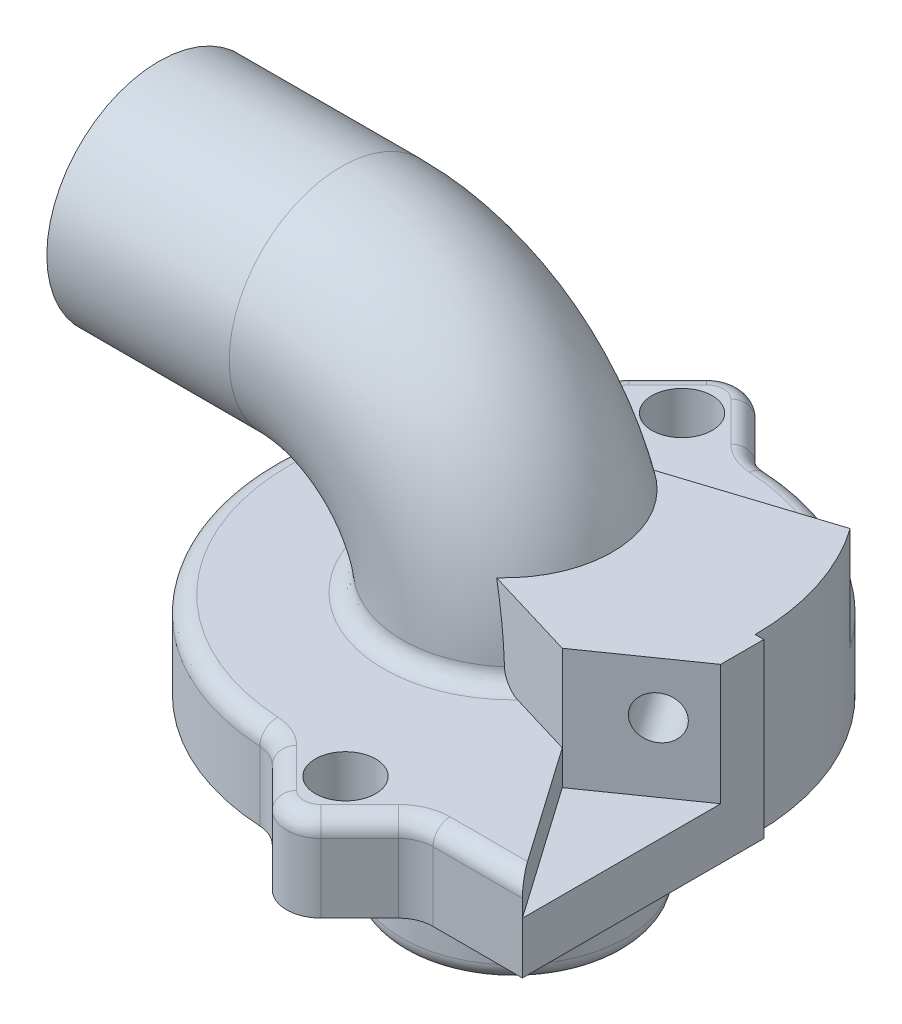
SolidWorks part; units mm, degrees
ref_plane "Front Plane" through (0, 0, 0) normal (0, 0, 1) x (1, 0, 0)
ref_plane "Top Plane" through (0, 0, 0) normal (0, 1, 0) x (1, 0, 0)
ref_plane "Right Plane" through (0, 0, 0) normal (1, 0, 0) x (0, 0, -1)
sketch "Sketch1" plane through (0, 0, 0) normal (0, 1, 0) x (1, 0, 0)
  circle A0 centre (0, 0) radius 14
  circle A1 centre (0, 0) radius 4.5
  dimension "D1" = 28
  dimension "D2" = 9
extrude "Boss-Extrude1" add sketch "Sketch1" along normal blind 5
sketch "Sketch5" plane through (0, 5, 0) normal (0, 1, 0) x (1, 0, 0)
  line L0 (0, -14) -> (4.2426, -18.2426)
  line L1 (14.5, -14) -> (14.5, 0)
  line L2 (14.5, 0) -> (14, 0)
  line L3 (14, 0) -> (0, -14)
  line L4 (4.2426, -18.2426) -> (8.4853, -14)
  line L5 (-2.75, 0) -> (2.75, 0) construction
  line L6 (0, -2.75) -> (0, 2.75) construction
  line L7 (8.4853, -14) -> (14.5, -14)
  line L8 (0, 14) -> (-4.2426, 18.2426)
  line L9 (-4.2426, 18.2426) -> (-8.4853, 14)
  line L10 (-8.4853, 14) -> (-8.4853, 11.1355)
  line L11 (-8.4853, 11.1355) -> (0, 14)
  circle A2 centre (0, 0) radius 14 construction
  dimension "D1" = 14.5
  dimension "D2" = 6
  dimension "D3" = 6
  dimension "D4" = 90
  dimension "D5" = 6
  dimension "D6" = 6
  dimension "D7" = 135
extrude "Boss-Extrude3" add sketch "Sketch5" against normal blind 5
sketch "Sketch6" plane through (0, 0, 0) normal (0, -1, 0) x (1, 0, 0)
  circle A0 centre (0, 0) radius 4.5
  circle A1 centre (0, 0) radius 6.5
  circle A2 centre (0, 0) radius 4.5 construction
  dimension "D1" = 2
extrude "Boss-Extrude4" add sketch "Sketch6" along normal blind 10
sketch "Sketch9" plane through (0, 5, 0) normal (0, 1, 0) x (1, 0, 0)
  line L0 (4.2426, -18.2426) -> (8.4853, -14) construction
  line L1 (0, -14) -> (4.2426, -18.2426) construction
  line L2 (-4.2426, 18.2426) -> (-8.4853, 14) construction
  line L3 (0, 14) -> (-4.2426, 18.2426) construction
  circle A0 centre (4.2426, -14) radius 1.75
  circle A1 centre (-4.2426, 14) radius 1.75
  dimension "D1" = 3.5
  dimension "D2" = 3
  dimension "D3" = 3
  dimension "D5" = 3
  dimension "D4" = 3
extrude "Cut-Extrude2" cut sketch "Sketch9" against normal blind 10
sketch "Sketch11" plane through (0, 5, 0) normal (0, 1, 0) x (1, 0, 0)
  line L0 (14.5, -14) -> (9.0968, -6.2834)
  line L1 (9.0968, -6.2834) -> (14.5, -2.5)
  line L3 (14.5, -14) -> (14.5, 0) construction
  line L4 (14.5, -2.5) -> (18.671, -8.4568) construction
  line L5 (14.5, -14) -> (14.5, -2.5)
  dimension "D1" = 35
  dimension "D2" = 11.5
extrude "Cut-Extrude3" cut sketch "Sketch11" against normal blind 2 contours L1 L5 L0
sketch "Sketch12" plane through (0, 5, 0) normal (0, 1, 0) x (1, 0, 0)
  line L0 (9.0968, -6.2834) -> (14.5, -2.5)
  line L1 (14.5, -2.5) -> (14.5, 0)
  line L2 (-8.25, 0) -> (8.25, 0) construction
  line L3 (14.5, 0) -> (14, 0)
  line L4 (9.0968, -6.2834) -> (3.1625, -4.4998)
  line L6 (2.0997, 5.0834) -> (11.4366, 8.075)
  arc A0 (14, 0) -> (11.4366, 8.075) centre (0, 0) ccw
  arc A2 (14, 0) -> (0, 14) centre (0, 0) ccw construction
  arc A3 (3.1625, -4.4998) -> (2.0997, 5.0834) centre (0, 0) ccw
  circle A4 centre (0, 0) radius 4.5 construction
  dimension "D1" = 1
extrude "Boss-Extrude5" add sketch "Sketch12" along normal blind 5
sketch "Sketch13" plane through (0, 0, 0) normal (0, 0, 1) x (1, 0, 0)
  line L0 (0, 5) -> (-14, 5) construction
  line L1 (0, -8.25) -> (0, 8.25) construction
  line L2 (-10, 15) -> (-20.5754, 15)
  arc A0 (0, 5) -> (-10, 15) centre (-10, 5) ccw
  dimension "D1" = 10
sketch "Sketch14" plane through (0, 5, 0) normal (0, 1, 0) x (1, 0, 0)
  circle A0 centre (0, 0) radius 4.5
  circle A1 centre (0, 0) radius 6.5
  circle A2 centre (0, 0) radius 4.5 construction
  dimension "D1" = 2
sweep "Sweep1" add profiles "Sketch14" path "Sketch13"
sketch "Sketch15" plane through (5.945, 0, 8.4903) normal (0.5736, 0, 0.8192) x (0.8192, 0, -0.5736)
  line L0 (3.8476, 10) -> (3.8476, 5) construction
  line L1 (3.8476, 10) -> (10.4438, 10) construction
  circle A0 centre (7.8476, 7) radius 1.25
  dimension "D1" = 2.5
  dimension "D2" = 4
  dimension "D3" = 3
extrude "Cut-Extrude4" cut sketch "Sketch15" against normal blind 25
fillet "Fillet1" radius 2 7 edges at (0, 2.5, 14) (8.4853, 2.5, 14) (4.2426, 2.5, 18.2426) (-8.4853, 2.5, -11.1355) (-8.4853, 2.5, -14) (0, 2.5, -14) (-4.2426, 2.5, -18.2426)
fillet "Fillet2" radius 1 19 edges at (0.0368, 5, -14.1506) (-1.6958, 5, -15.6958) (-4.2426, 5, -17.4142) (-6.7782, 5, -15.7071) (-8.333, 5, -13.9369) (-8.4853, 5, -12.6285) (-8.6658, 5, -11.2552) (11.9069, 5, 14) (8.5483, 5, 14.1522) (6.7782, 5, 15.7071) (4.2426, 5, 17.4142) (1.6958, 5, 15.6958) (-0.0368, 5, 14.1506) (0, -10, -6.5) (0, -10, -4.5) (0, 0, 6.5) (-13.2414, 5, 4.5459) (-6.4764, 5, 0.5531)
